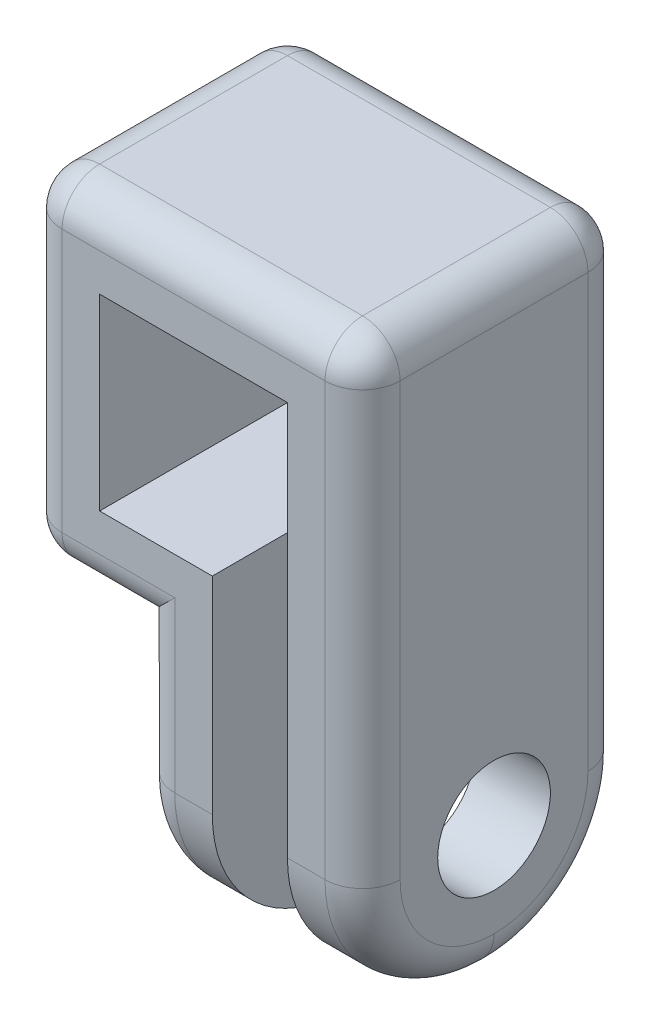
SolidWorks part; units mm, degrees
ref_plane "前视基准面" through (0, 0, 0) normal (0, 0, 1) x (1, 0, 0)
ref_plane "上视基准面" through (0, 0, 0) normal (0, 1, 0) x (1, 0, 0)
ref_plane "右视基准面" through (0, 0, 0) normal (1, 0, 0) x (0, 0, -1)
sketch "草图1" plane through (0, 0, 0) normal (0, 0, 1) x (1, 0, 0)
  line L0 (0, 6.4547) -> (0, -8.4381) construction
  line L1 (-2.5, 2.5) -> (2.5, 2.5)
  line L2 (-2.5, 2.5) -> (-2.5, -2.5)
  line L3 (-2.5, -2.5) -> (2.5, -2.5)
  line L4 (2.5, 2.5) -> (2.5, -2.5)
  line L5 (-2.5, 2.5) -> (2.5, -2.5) construction
  line L6 (-2.5, -2.5) -> (2.5, 2.5) construction
  line L7 (-4.5, 4.5) -> (4.5, 4.5)
  line L8 (-4.5, 4.5) -> (-4.5, -4.5)
  line L9 (-4.5, -4.5) -> (4.5, -4.5)
  line L10 (4.5, 4.5) -> (4.5, -4.5)
  line L11 (-4.5, 4.5) -> (4.5, -4.5) construction
  line L12 (-4.5, -4.5) -> (4.5, 4.5) construction
  line L13 (4.5, -4.5) -> (4.5, -11.5)
  line L14 (4.5, -11.5) -> (2.5, -11.5)
  line L15 (2.5, -11.5) -> (2.5, -2.5)
  line L16 (0.5, -4.5) -> (0.5, -11.5)
  line L17 (0.5, -11.5) -> (-1.5, -11.5)
  line L18 (-1.5, -11.5) -> (-1.5, -4.5)
  line L19 (0.5, -4.5) -> (0.5, -2.5)
  point P0 (0, 0)
  point P5 (0, 0)
  dimension "D1" = 5
  dimension "D2" = 5
  dimension "D3" = 9
  dimension "D4" = 9
  dimension "D5" = 7
  dimension "D6" = 4
  dimension "D7" = 7
  dimension "D8" = 2
extrude "凸台-拉伸2" add sketch "草图1" along normal blind 7 contours L9 L19 L3 L2 L1 L4 L15 L10 L7 L8 | L18 L17 L16 L9 | L15 L14 L13 L9 region at (-2.6273, 0, 0) region at (3.5, -8, 0) region at (-0.5, -8, 0)
fillet "圆角4" radius 3.5 4 edges at (3.5, -11.5, 0) (3.5, -11.5, 7) (-0.5, -11.5, 0) (-0.5, -11.5, 7)
sketch "草图3" plane through (-1.5, 0, 0) normal (-1, 0, 0) x (0, 0, 1)
  circle A0 centre (3.5, -8) radius 1.5
  dimension "D1" = 3
extrude "切除-拉伸2" cut sketch "草图3" against normal through all
fillet "圆角5" radius 1 17 edges at (4.5, -1.75, 0) (4.5, -10.4749, 1.0251) (4.5, -10.4749, 5.9749) (-1.5, -6.25, 0) (-1.5, -10.4749, 1.0251) (-1.5, -10.4749, 5.9749) (-3, -4.5, 0) (4.5, 4.5, 3.5) (0, 4.5, 0) (4.5, -1.75, 7) (0, 4.5, 7) (-4.5, 4.5, 3.5) (-4.5, 0, 7) (-4.5, 0, 0) (-4.5, -4.5, 3.5) (-1.5, -6.25, 7) (-3, -4.5, 7)
